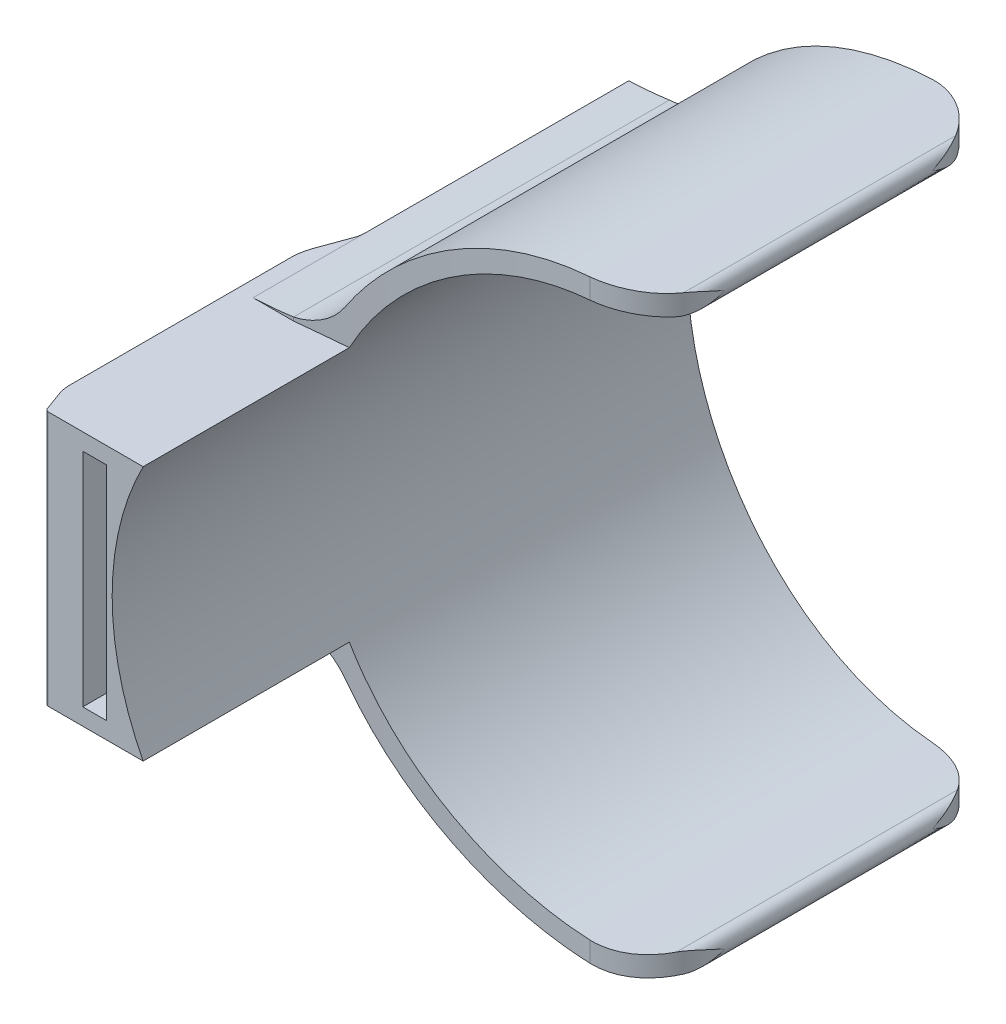
SolidWorks part; units mm, degrees
ref_plane "前视基准面" through (0, 0, 0) normal (0, 0, 1) x (1, 0, 0)
ref_plane "上视基准面" through (0, 0, 0) normal (0, 1, 0) x (1, 0, 0)
ref_plane "右视基准面" through (0, 0, 0) normal (1, 0, 0) x (0, 0, -1)
sketch "Sketch3" plane through (0, 0, 0) normal (0, 0, 1) x (1, 0, 0)
  line L1 (-4.5, 19) -> (4.5, 19)
  line L2 (-4.5, 19) -> (-4.5, -19)
  line L3 (-4.5, -19) -> (4.5, -19)
  line L4 (4.5, 19) -> (4.5, -19)
  line L5 (-4.5, 19) -> (4.5, -19) construction
  line L6 (-4.5, -19) -> (4.5, 19) construction
  point P0 (0, 0)
  dimension "D1" = 38
  dimension "D2" = 9
extrude "Boss-Extrude1" add sketch "Sketch3" along normal mid plane 56
sketch "Sketch4" plane through (0, 0, 0) normal (0, 0, 1) x (1, 0, 0)
  line L0 (-24.0082, 0) -> (58.1501, 0) construction
  line L1 (51.5, 41) -> (51.5, -41) construction
  line L2 (4.5, -19) -> (4.5, 19) construction
  line L3 (-4.5, 19) -> (-4.5, -19) construction
  line L4 (-4.5, 19) -> (-4.5, -19)
  arc A0 (51.5, 41) -> (51.5, -41) centre (45.883, 0) ccw
  arc A1 (51.9072, 43.9722) -> (8.5621, 24.0208) centre (45.883, 0) ccw
  arc A2 (-4.5, 19) -> (1.5322, 19.5285) centre (-6.6658, 78.4116) ccw
  arc A3 (8.5621, -24.0208) -> (51.9072, -43.9722) centre (45.883, 0) ccw
  arc A4 (51.9072, 43.9722) -> (51.9072, -43.9722) centre (45.883, 0) ccw construction
  arc A5 (1.5322, 19.5285) -> (8.5621, 24.0208) centre (0.1532, 29.4329) ccw
  arc A6 (1.5322, -19.5285) -> (8.5621, -24.0208) centre (0.1532, -29.4329) cw
  arc A7 (-4.5, -19) -> (1.5322, -19.5285) centre (-6.6658, -78.4116) cw
  arc A8 (51.5, 41) -> (51.9072, 43.9722) centre (51.7036, 42.4861) ccw
  arc A9 (51.5, -41) -> (51.9072, -43.9722) centre (51.7036, -42.4861) cw
  point P5 (51.5, 0)
  dimension "D4" = 10
  dimension "D1" = 47
  dimension "D2" = 82
  dimension "D3" = 3
extrude "Boss-Extrude3" add sketch "Sketch4" along normal mid plane 56
ref_plane "Plane1" through (0, 45, 0) normal (0, 1, 0) x (1, 0, 0)
sketch "Sketch5" plane through (0, 45, 0) normal (0, 1, 0) x (1, 0, 0)
  line L0 (-35.9872, 0) -> (71.5426, 0) construction
  line L1 (53.2036, 15) -> (53.2036, -15)
  line L2 (53.2036, -28) -> (53.2036, 28) construction
  line L3 (43.2036, 25.5) -> (43.2036, -25.5) construction
  line L4 (1.5322, 0) -> (1.5322, -28)
  line L5 (1.5322, 28) -> (53.2036, 28)
  line L6 (53.2036, 28) -> (53.2036, 15)
  line L7 (53.2036, -15) -> (53.2036, -28)
  line L8 (53.2036, -28) -> (1.5322, -28)
  arc A0 (43.2036, 25.5) -> (53.2036, 15) centre (43.0362, 15.3286) cw
  arc A1 (53.2036, -15) -> (43.2036, -25.5) centre (42.9536, -15.25) cw
  arc A2 (43.2036, 25.5) -> (1.5322, 28) centre (51.1102, 505.8437) cw
  arc A3 (43.2036, -25.5) -> (1.5322, -28) centre (51.1102, -505.8437) ccw
  point P7 (53.2036, 0)
  point P10 (43.2036, 0)
  dimension "D1" = 30
  dimension "D2" = 51
  dimension "D3" = 10
extrude "Cut-Extrude1" cut sketch "Sketch5" against normal up to next contours A2 A0 L6 L5 | A1 A3 L8 L7 region at (37.0704, 45, 26.214) region at (37.0293, 45, -26.2277)
sketch "Sketch7" plane through (0, 0, 0) normal (0, 0, 1) x (1, 0, 0)
  line L0 (-4.5, 19) -> (9.1195, 19)
  line L1 (-4.5, -19) -> (9.1195, -19)
  line L2 (-4.5, 19) -> (-6.8805, 19)
  line L3 (-6.8805, 19) -> (-6.8805, -19)
  line L4 (-6.8805, -19) -> (-4.5, -19)
  arc A0 (43.2036, 41.2961) -> (43.2036, -41.2961) centre (45.883, 0) ccw construction
  arc A1 (9.1195, 19) -> (9.1195, -19) centre (45.883, 0) ccw
  dimension "D1" = 16
extrude "Boss-Extrude4" add sketch "Sketch7" along normal blind 58
sketch "Sketch8" plane through (0, -19, 0) normal (0, -1, 0) x (1, 0, 0)
  line L2 (-4.7412, 12.6628) -> (-6.398, 17.2147)
  line L3 (-6.8805, 58) -> (-6.8805, 0) construction
  line L4 (-4.5, 11.2947) -> (-4.5, 0)
  line L5 (-4.5, 0) -> (-6.8805, 0)
  line L7 (-4.5, 0) -> (-4.5, 12)
  line L8 (-6.8805, 0) -> (-6.8805, 19.9509)
  line L9 (-6.5789, 54.7342) -> (-5.51, 57.671)
  line L10 (-6.8805, 58) -> (9.1195, 58) construction
  line L13 (-6.8805, 53.0241) -> (-6.8805, 58)
  line L14 (-6.8805, 58) -> (-5.0402, 58)
  arc A0 (-6.398, 17.2147) -> (-6.8805, 19.9509) centre (1.1195, 19.9509) cw
  arc A1 (-4.7412, 12.6628) -> (-4.5, 11.2947) centre (-8.5, 11.2947) cw
  arc A2 (-6.5789, 54.7342) -> (-6.8805, 53.0241) centre (-1.8805, 53.0241) ccw
  arc A3 (-5.51, 57.671) -> (-5.0402, 58) centre (-5.0402, 57.5) cw
  point P17 (-6.8805, 18.5403)
  point P22 (-6.8805, 53.9058)
  point P26 (-5.3903, 58)
  line M3 (-6.8805, 0) -> (-4.5, 0)
  line M4 (-4.5, 0) -> (-4.5, 28)
  line M8 (9.1195, 58) -> (-6.8805, 58)
  line M9 (-6.8805, 58) -> (-6.8805, 0)
  dimension "D2" = 8
  dimension "D1" = 4
  dimension "D3" = 5
  dimension "D4" = 0.5
extrude "Cut-Extrude2" cut sketch "Sketch8" against normal up to next contours A1 L2 A0 M9 M3 M4 | L9 A3 A2 M8 M9 region at (-5.7793, -19, 7.7825) region at (-6.3825, -19, 56.6051)
sketch "Sketch9" plane through (0, 0, 58) normal (0, 0, 1) x (1, 0, 0)
  line L0 (-6.8805, 19) -> (-6.8805, -19) construction
  line L1 (3.6595, -16.5) -> (0.1195, -16.5)
  line L2 (3.6595, -16.5) -> (3.6595, 16.5)
  line L3 (3.6595, 16.5) -> (0.1195, 16.5)
  line L4 (0.1195, -16.5) -> (0.1195, 16.5)
  line L5 (3.6595, -16.5) -> (0.1195, 16.5) construction
  line L6 (3.6595, 16.5) -> (0.1195, -16.5) construction
  point P0 (1.8895, 0)
  point P7 (0, 0)
  dimension "D1" = 7
  dimension "D2" = 33
  dimension "D3" = 3.54
extrude "Cut-Extrude3" cut sketch "Sketch9" against normal blind 57
